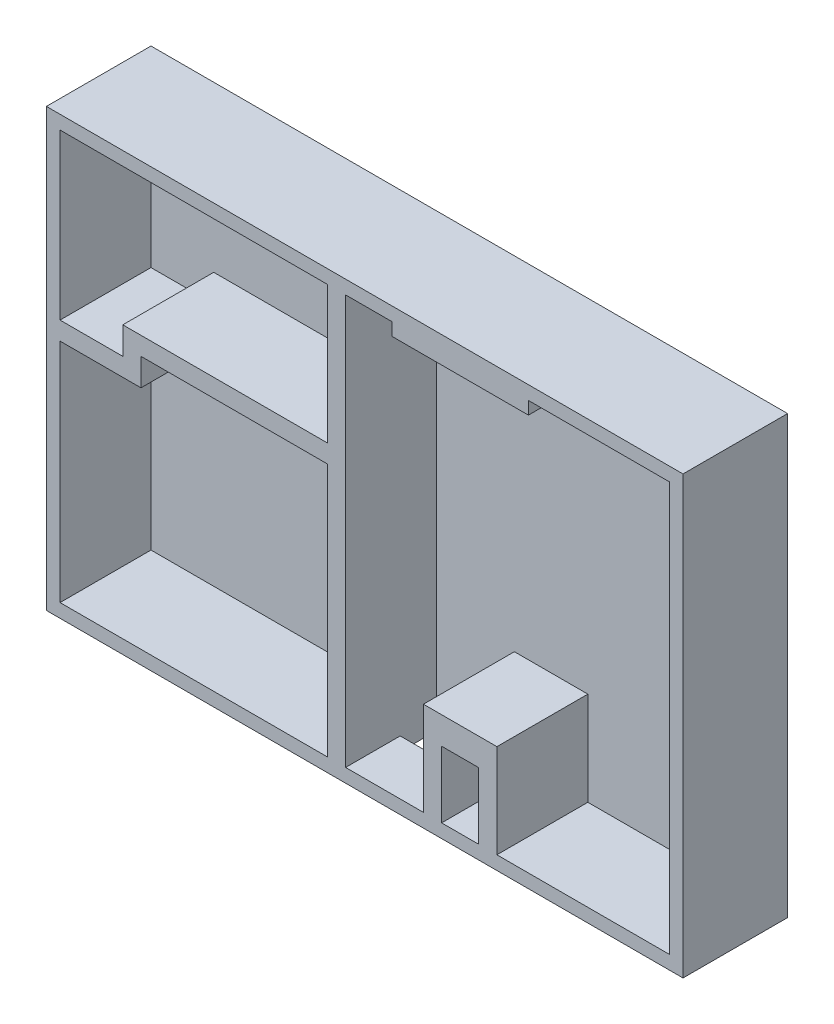
SolidWorks part; units mm, degrees
ref_plane "前视基准面" through (0, 0, 0) normal (0, 0, 1) x (1, 0, 0)
ref_plane "上视基准面" through (0, 0, 0) normal (0, 1, 0) x (1, 0, 0)
ref_plane "右视基准面" through (0, 0, 0) normal (1, 0, 0) x (0, 0, -1)
sketch "草图1" plane through (0, 0, 0) normal (0, 0, 1) x (1, 0, 0)
  line L1 (-35, 24) -> (35, 24)
  line L2 (-35, 24) -> (-35, -24)
  line L3 (-35, -24) -> (35, -24)
  line L4 (35, 24) -> (35, -24)
  line L5 (-35, 24) -> (35, -24) construction
  line L6 (-35, -24) -> (35, 24) construction
  point P0 (0, 0)
  dimension "D1" = 48
  dimension "D2" = 70
extrude "凸台-拉伸1" add sketch "草图1" along normal blind 11.5
shell "抽壳1" thickness 1.5 removed face at (0, 0, 11.5)
sketch "草图2" plane through (0, 0, 1.5) normal (0, 0, 1) x (1, 0, 0)
  line L0 (-26.6, 7.4) -> (-4.1, 7.4)
  line L1 (-33.5, 22.5) -> (-33.5, -22.5) construction
  line L12 (12.536, -22.5) -> (12.536, -15.2)
  line L13 (12.536, -15.2) -> (8.456, -15.2)
  line L14 (-4.1, -22.5) -> (-4.1, 5.4)
  line L15 (-4.1, 5.4) -> (-24.6, 5.4)
  line L17 (-4.1, 22.5) -> (-4.1, 7.4)
  line L18 (33.5, 22.5) -> (-33.5, 22.5) construction
  line L20 (-4.1, 22.5) -> (-2.1, 22.5)
  line L21 (3, 22.5) -> (3, 21.1)
  line L22 (3, 21.1) -> (18, 21.1)
  line L23 (18, 21.1) -> (18, 22.5)
  line L24 (18, 22.5) -> (3, 22.5)
  line L28 (-2.1, 22.5) -> (-2.1, -22.5)
  line L29 (-4.2, 12) -> (-4.2, 18) construction
  line L30 (-6.2, 7.5) -> (-26.7, 7.5) construction
  line L31 (-26.6, 7.4) -> (-26.6, 4.4)
  line L32 (-26.6, 4.4) -> (-33.5, 4.4)
  line L34 (-33.5, 2.4) -> (-24.6, 2.4)
  line L35 (-24.6, 2.4) -> (-24.6, 5.4)
  line L36 (-26.7, 4.5) -> (-32.2, 4.5) construction
  line L37 (-26.7, 4.5) -> (-26.7, 7.5) construction
  line L38 (10.5, 22.5) -> (10.5, 14.3773) construction
  line L39 (11.5, 22.5) -> (9.5, 22.5) construction
  line L49 (14.536, -12.2) -> (6.456, -12.2)
  line L50 (6.456, -12.2) -> (6.456, -22.5)
  line L52 (8.456, -22.5) -> (8.456, -15.2)
  line L55 (-33.5, -22.5) -> (33.5, -22.5) construction
  line L56 (14.536, -12.2) -> (14.536, -22.5)
  line L57 (12.536, -22.5) -> (14.536, -22.5)
  line L58 (14.636, -14.05) -> (14.636, -21.55) construction
  line L59 (8.456, -22.5) -> (6.456, -22.5)
  line L60 (-33.5, 2.4) -> (-33.5, 4.4)
  line L61 (-2.1, -22.5) -> (-4.1, -22.5)
  dimension "D2" = 0.1
  dimension "D3" = 2
  dimension "D4" = 7.3
  dimension "D6" = 2
  dimension "D7" = 2
  dimension "D8" = 2
  dimension "D9" = 0.1
  dimension "D10" = 3
  dimension "D11" = 0.1
  dimension "D12" = 2
  dimension "D14" = 0.1
  dimension "D15" = 0.1
  dimension "D16" = 1.4
  dimension "D17" = 15
  dimension "D18" = 2
  dimension "D19" = 4.08
extrude "凸台-拉伸2" add sketch "草图2" along normal up to surface (10 mm away) up to face at (0, 0, 11.5)
sketch "草图4" plane through (0, -24, 0) normal (0, -1, 0) x (1, 0, 0)
  line L1 (-2.1, 5.5) -> (1.9, 5.5)
  line L2 (-2.1, 5.5) -> (-2.1, 1.5)
  line L3 (-2.1, 1.5) -> (1.9, 1.5)
  line L4 (1.9, 5.5) -> (1.9, 1.5)
  line L6 (-2.1, 1.5) -> (-2.1, 11.5) construction
  line L7 (-33.5, 1.5) -> (-4.1, 1.5) construction
  dimension "D1" = 4
  dimension "D2" = 4
extrude "切除-拉伸2" cut sketch "草图4" against normal up to next
